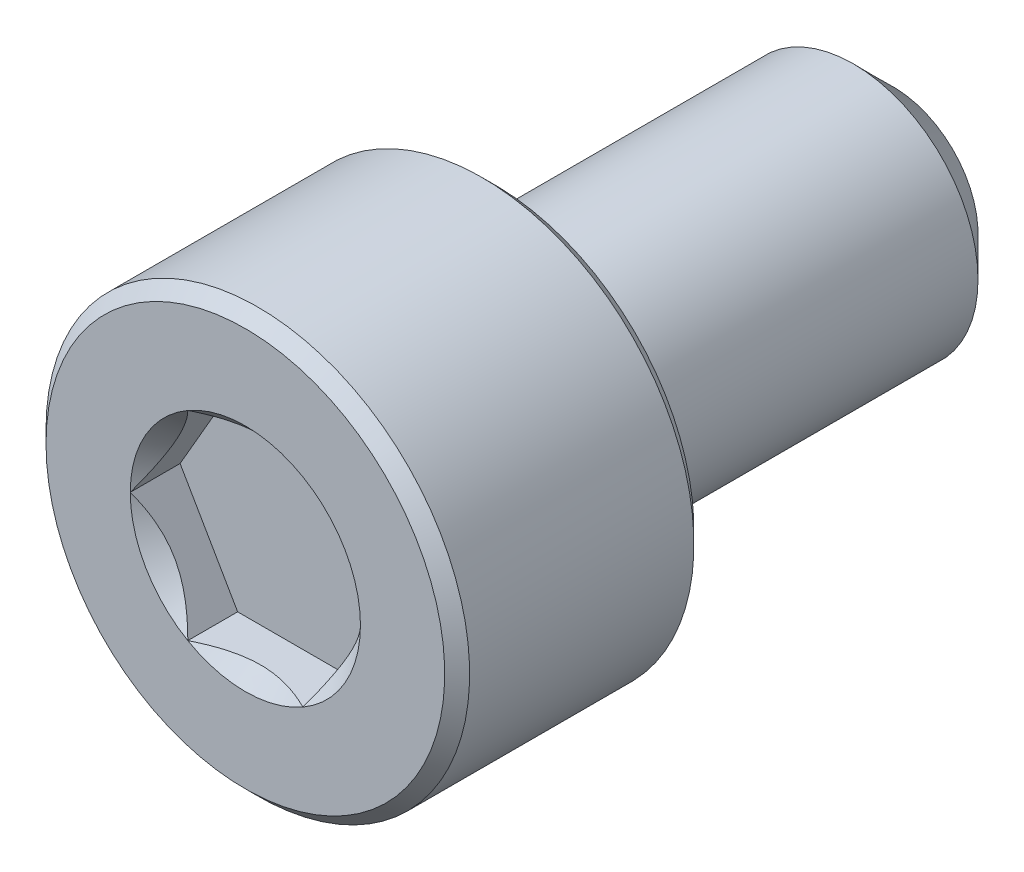
SolidWorks part; units mm, degrees
ref_plane "Front Plane" through (0, 0, 0) normal (0, 0, 1) x (1, 0, 0)
ref_plane "Top Plane" through (0, 0, 0) normal (0, 1, 0) x (1, 0, 0)
ref_plane "Right Plane" through (0, 0, 0) normal (1, 0, 0) x (0, 0, -1)
sketch "Sketch1" plane through (0, 0, 0) normal (1, 0, 0) x (0, 0, -1)
  line L0 (-6.5, 0) -> (6.5, 0) construction
  line L1 (6.5, 0) -> (6.5, 1.7) construction
  line L2 (6.5, 1.7) -> (5.7, 2.5) construction
  line L3 (5.7, 2.5) -> (-11.5, 2.5) construction
  line L5 (-1.5, 3) -> (-1.5, 4.25) construction
  line L6 (-1.5, 4.25) -> (-6.5, 4.25) construction
  line L7 (-6.5, 4.25) -> (-6.5, 0) construction
  line L8 (6.5, 1.7) -> (6.5, 2.5) construction
  line L9 (6.45, 2.5866) -> (6.85, 1.8938) construction
  line L10 (6.85, 1.8938) -> (7.25, 2.5866) construction
  line L11 (7.25, 2.5866) -> (6.45, 2.5866) construction
  line L12 (6.85, 2.5866) -> (6.85, 2.5) construction
  line L13 (6.85, 1.8938) -> (6.85, 1.9804) construction
  line L14 (6.8, 1.9804) -> (6.9, 1.9804) construction
  line L15 (6.5, 2.5) -> (7.2, 2.5) construction
  line L16 (6.475, 2.5433) -> (7.225, 2.5433) construction
  line L17 (6.5, 0) -> (6.5, -2.5) construction
  line L18 (-1.75, 4.25) -> (-1.5, 4) construction
  line L19 (-6.25, 4.25) -> (-6.5, 4) construction
  point P0 (-6.5, 2)
  point P3 (3.7, 2.5)
  point P4 (0, 0)
  point P22 (6.85, 1.9804)
  point P24 (-11.5, 2.5)
  point P25 (6.85, 2.5)
  point P28 (6.85, 2.5433)
  point P29 (3.7, -2.5)
  point P31 (-4, 4.25)
  point P37 (-2.375, 4.25)
  point P38 (-6.125, 4.25)
  dimension "head height" = 5
  dimension "D1" = 45
  dimension "head dia" = 8.5
  dimension "thread dia" = 5
  dimension "drive size" = 4
  dimension "pitch" = 0.8
  dimension "D2" = 0.1
  dimension "D3" = 0.8
  dimension "D4" = 2.8
  dimension "D7" = 0.25
  dimension "D8" = 0.25
  dimension "D9" = 0.25
  dimension "D10" = 0.125
  dimension "D11" = 0.625
  dimension "D12" = 18
sketch "Sketch2" plane through (0, 0, 0) normal (1, 0, 0) x (0, 0, -1)
  line L1 (-6.25, 4.25) -> (-1.75, 4.25)
  line L4 (5.7, 2.5) -> (6.5, 1.7)
  line L5 (6.5, 1.7) -> (6.5, 0)
  line L6 (-1.75, 4.25) -> (-1.5, 4) construction
  line L7 (6.5, 0) -> (-6.5, 0)
  line L8 (-6.25, 4.25) -> (-6.5, 4) construction
  line L9 (-1.75, 4.25) -> (-1.5, 4)
  line L10 (-6.25, 4.25) -> (-6.5, 4)
  line L11 (-6.5, 4) -> (-6.5, 0)
  line L12 (-1.5, 4) -> (-1.5, 2.5)
  line L13 (-1.5, 2.5) -> (5.7, 2.5)
revolve "Revolve1" add sketch "Sketch2" angle 360 about L7
sketch "Sketch3" plane through (0, 0, 6.5) normal (0, 0, 1) x (1, 0, 0)
  line L1 (1.1547, 2) -> (-1.1547, 2)
  line L2 (-1.1547, 2) -> (-2.3094, 0)
  line L3 (-2.3094, 0) -> (-1.1547, -2)
  line L4 (-1.1547, -2) -> (1.1547, -2)
  line L5 (1.1547, -2) -> (2.3094, 0)
  line L6 (2.3094, 0) -> (1.1547, 2)
  circle A0 centre (0, 0) radius 2 construction
extrude "Cut-Extrude1" cut sketch "Sketch3" against normal offset from surface (1 mm away) 1 up to face at (-4, 0, 6.5)
sketch "Sketch4" plane through (0, 0, 6.5) normal (0, 0, 1) x (1, 0, 0)
  circle A0 centre (0, 0) radius 2.3094
extrude "Cut-Extrude2" cut sketch "Sketch4" against normal blind 0.5 draft 45
ref_plane "Plane1" [suppressed] through (0, 0, 11.5) normal (0, 0, 1) x (1, 0, 0)
split "Split1" [suppressed] bodies to split 106
sketch "Sketch6" [suppressed] plane through (0, 0, -6.5) normal (0, 0, -1) x (-1, 0, 0)
  circle A0 centre (0, 0) radius 2.5
curve "Helix/Spiral1" [suppressed] pitch 0.8 height 8.8 turns 11
sketch "Sketch7" [suppressed] plane through (0, 0, 0) normal (1, 0, 0) x (0, 0, -1)
  line L0 (6.475, 2.5433) -> (7.225, 2.5433)
  line L1 (7.225, 2.5433) -> (6.9, 1.9804)
  line L2 (6.9, 1.9804) -> (6.8, 1.9804)
  line L3 (6.8, 1.9804) -> (6.475, 2.5433)
sweep "Cut-Sweep1" [suppressed] cut profiles "Sketch7" path "Helix/Spiral1"
sketch "Sketch8" [suppressed] plane through (0, 0, 1.5) normal (0, 0, -1) x (-1, 0, 0)
  circle A0 centre (0, 0) radius 2.5
extrude "Boss-Extrude1" [suppressed] add sketch "Sketch8" along normal through all draft 45
ref_plane "Plane2" [suppressed] through (0, 0, 4) normal (0, 0, 1) x (1, 0, 0)
sketch "Sketch9" [suppressed] plane through (0, 0, 4) normal (0, 0, 1) x (1, 0, 0)
  line L0 (0, 4.0375) -> (0.0742, 4.2494)
  line L1 (0, 4.0375) -> (-0.0742, 4.2494)
  line L2 (0, 4.25) -> (0, 0) construction
  line L3 (-0.0742, 4.2494) -> (0, 0) construction
  line L4 (0, 0) -> (0.0742, 4.2494) construction
  arc A0 (0.0742, 4.2494) -> (-0.0742, 4.2494) centre (0, 0) ccw
  circle A1 centre (0, 0) radius 4.0375 construction
  dimension "D1" = 8.5
  dimension "D2" = 8.075
  dimension "D3" = 2
extrude "Cut-Extrude4" [suppressed] cut sketch "Sketch9" against normal up to vertex and the other way up to vertex
pattern_circular "CirPattern2" [suppressed] count 175 over 360 about axis through (0, 0, 6.5) along (0, 0, -1) of bodies 113
equation "\"D2@Sketch1\"=\"pitch@Sketch1\"/8"
equation "\"D3@Sketch1\"=\"pitch@Sketch1\""
equation "\"D3@Helix/Spiral1\"=\"length@Sketch1\"+\"pitch@Sketch1\""
equation "\"D4@Helix/Spiral1\"=\"pitch@Sketch1\""
equation "\"D4@Sketch1\"=\"pitch@Sketch1\"*3.5"
equation "\"D7@Sketch1\"=\"head height@Sketch1\"*.05"
equation "\"D8@Sketch1\"=\"D7@Sketch1\""
equation "\"D9@Sketch1\"=\"D7@Sketch1\""
equation "\"D10@Sketch1\"=\"D7@Sketch1\"/2"
equation "\"D11@Sketch1\"=\"D10@Sketch1\"*5"
equation "\"D2@Sketch9\"=\"D1@Sketch9\"*.95"
equation "\"D1@CirPattern2\"= ( 360 / \"D3@Sketch9\" ) - 5"
